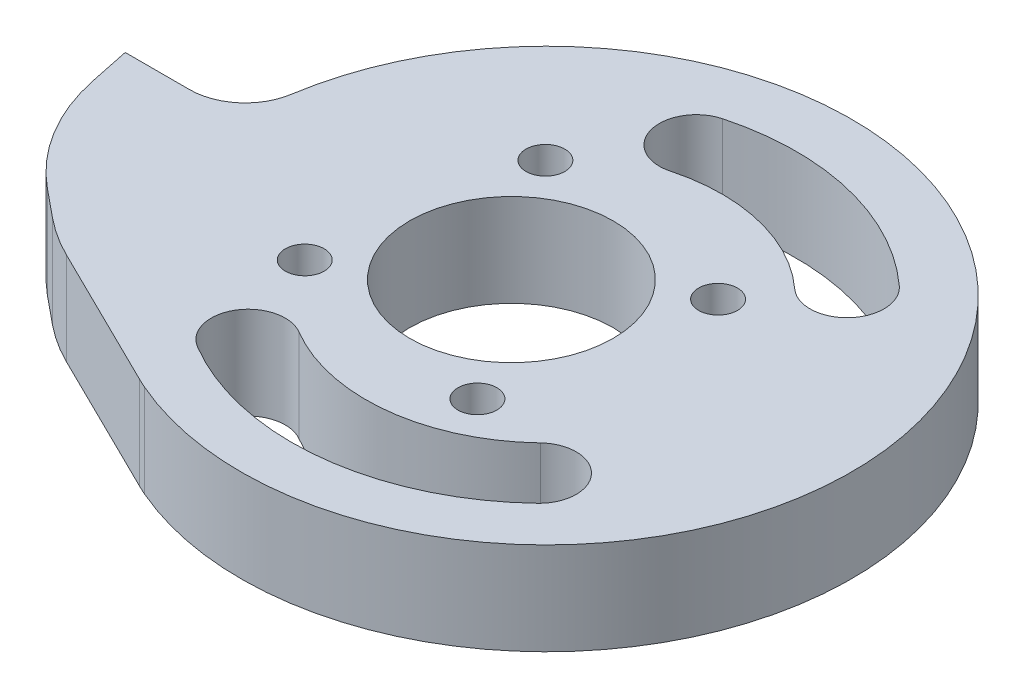
SolidWorks part; units mm, degrees
material "ABS"
ref_plane "Front Plane" through (0, 0, 0) normal (0, 0, 1) x (1, 0, 0)
ref_plane "Top Plane" through (0, 0, 0) normal (0, 1, 0) x (1, 0, 0)
ref_plane "Right Plane" through (0, 0, 0) normal (1, 0, 0) x (0, 0, -1)
sketch "Sketch1" plane through (0, 0, 0) normal (0, 1, 0) x (1, 0, 0)
  line L0 (-33, 0) -> (-45.5, 0)
  line L1 (-45.5, 0) -> (-43, -12)
  line L3 (-43, -12) -> (-32, -21)
  line L4 (-32, -21) -> (-13.7477, -30)
  circle A3 centre (-3.38, -0.39) radius 11
  arc A4 (-33, 0) -> (-13.7477, -30) centre (0, 0) cw
  dimension "D1" = 11
  dimension "D2" = 12.5
  dimension "D8" = 22
  dimension "D10" = 33
  dimension "D3" = 12
  dimension "D4" = 2.5
  dimension "D5" = 9
  dimension "D6" = 3.38
  dimension "D7" = 0.39
  dimension "D9" = 9
extrude "Boss-Extrude1" add sketch "Sketch1" along normal blind 10
sketch "Sketch2" plane through (0, 10, 0) normal (0, 1, 0) x (1, 0, 0)
  circle A0 centre (9.62, 8.9374) radius 2.1
  circle A1 centre (-3.38, -0.39) radius 11 construction
  circle A2 centre (5.9474, -13.39) radius 2.1
  circle A3 centre (-16.38, -9.7174) radius 2.1
  circle A4 centre (-12.7074, 12.61) radius 2.1
  point P17 (-3.38, -0.39)
  dimension "D2" = 4.2
  dimension "D1" = 16
  dimension "D4" = 0
  dimension "D5" = 0
  dimension "D6" = 13
  dimension "D3" = 4
extrude "Cut-Extrude1" cut sketch "Sketch2" against normal through all
sketch "Sketch4" plane through (0, 10, 0) normal (0, 1, 0) x (1, 0, 0)
  arc A0 (-12, -20.2052) -> (16.225, -17) centre (0, 0) ccw construction
  arc A1 (-14.0426, -23.6444) -> (18.9867, -19.8936) centre (0, 0) ccw
  arc A2 (-9.9574, -16.766) -> (13.4633, -14.1064) centre (0, 0) ccw
  arc A3 (-9.9574, -16.766) -> (-14.0426, -23.6444) centre (-12, -20.2052) ccw
  arc A4 (18.9867, -19.8936) -> (13.4633, -14.1064) centre (16.225, -17) ccw
  arc A5 (15.4919, 17) -> (-6, 22.2036) centre (0, 0) ccw construction
  arc A6 (18.1862, 19.9565) -> (-7.0435, 26.0651) centre (0, 0) ccw
  arc A7 (12.7977, 14.0435) -> (-4.9565, 18.3421) centre (0, 0) ccw
  arc A8 (12.7977, 14.0435) -> (18.1862, 19.9565) centre (15.4919, 17) ccw
  arc A9 (-7.0435, 26.0651) -> (-4.9565, 18.3421) centre (-6, 22.2036) ccw
  point P4 (2.6516, -23.3499)
  point P12 (5.4124, 22.3541)
  dimension "D1" = 23.5
  dimension "D2" = 4
  dimension "D5" = 23
  dimension "D6" = 4
  dimension "D3" = 12
  dimension "D4" = 17
  dimension "D7" = 17
  dimension "D8" = 6
extrude "Cut-Extrude3" cut sketch "Sketch4" against normal blind 10
fillet "Fillet1" radius 6 1 edges at (-33, 5, 0)
fillet "Fillet2" radius 22 3 edges at (-13.7477, 5, 30) (-32, 5, 21) (-43, 5, 12)
